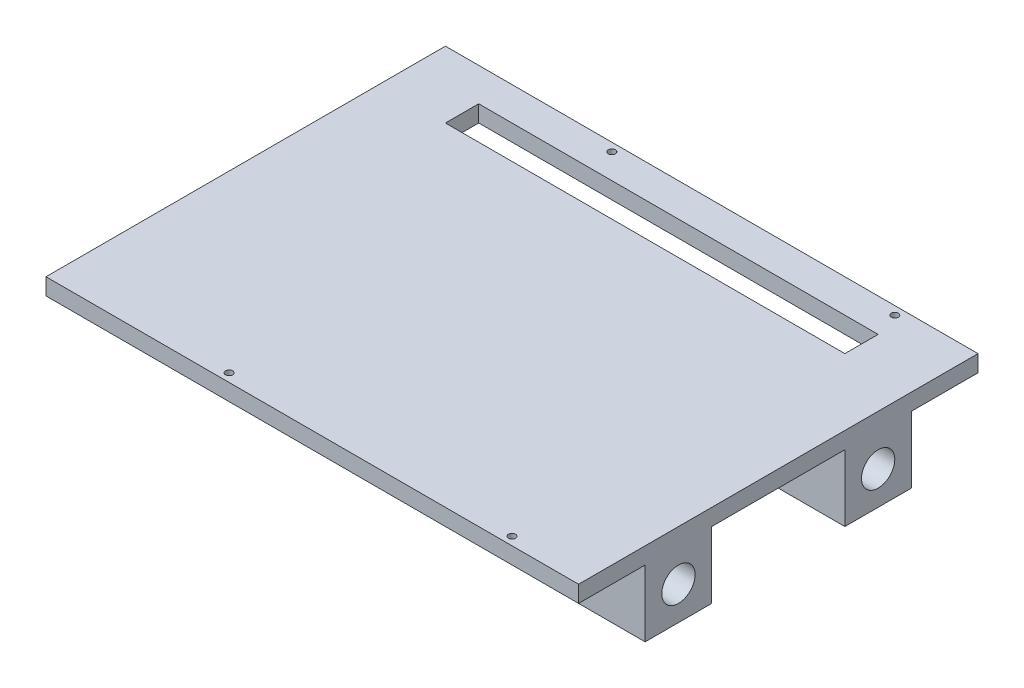
SolidWorks part; units mm, degrees
ref_plane "Front Plane" through (0, 0, 0) normal (0, 0, 1) x (1, 0, 0)
ref_plane "Top Plane" through (0, 0, 0) normal (0, 1, 0) x (1, 0, 0)
ref_plane "Right Plane" through (0, 0, 0) normal (1, 0, 0) x (0, 0, -1)
sketch "Sketch2" plane through (0, 0, 0) normal (0, 1, 0) x (1, 0, 0)
  line L1 (-101.6, -76.2) -> (101.6, -76.2)
  line L2 (-101.6, -76.2) -> (-101.6, 76.2)
  line L3 (-101.6, 76.2) -> (101.6, 76.2)
  line L4 (101.6, -76.2) -> (101.6, 76.2)
  line L5 (-101.6, -76.2) -> (101.6, 76.2) construction
  line L6 (-101.6, 76.2) -> (101.6, -76.2) construction
  point P0 (0, 0)
  dimension "D1" = 203.2
  dimension "D2" = 152.4
extrude "Boss-Extrude1" add sketch "Sketch2" along normal blind 6.35
sketch "Sketch3" plane through (0, 6.35, 0) normal (0, 1, 0) x (1, 0, 0)
  line L0 (-101.6, 0) -> (101.6, 0) construction
  line L1 (-101.6, 76.2) -> (-101.6, -76.2) construction
  line L2 (101.6, -76.2) -> (101.6, 76.2) construction
  line L3 (0, 76.2) -> (0, -76.2) construction
  line L4 (101.6, 76.2) -> (-101.6, 76.2) construction
  line L5 (-101.6, -76.2) -> (101.6, -76.2) construction
  line L7 (-76.2, 63.5) -> (76.2, 63.5)
  line L8 (-76.2, 63.5) -> (-76.2, 50.8)
  line L9 (-76.2, 50.8) -> (76.2, 50.8)
  line L10 (76.2, 63.5) -> (76.2, 50.8)
  line L11 (-76.2, 63.5) -> (76.2, 50.8) construction
  line L12 (-76.2, 50.8) -> (76.2, 63.5) construction
  point P12 (0, 57.15)
  dimension "D1" = 12.7
  dimension "D2" = 152.4
  dimension "D3" = 12.7
extrude "Cut-Extrude1" cut sketch "Sketch3" against normal blind 6.35
sketch "Sketch4" plane through (0, 0, 0) normal (0, -1, 0) x (1, 0, 0)
  line L0 (-101.6, -76.2) -> (-101.6, 76.2) construction
  line L1 (-101.6, 50.8) -> (-50.8, 50.8)
  line L2 (-101.6, 50.8) -> (-101.6, 25.4)
  line L3 (-101.6, 25.4) -> (-50.8, 25.4)
  line L4 (-50.8, 50.8) -> (-50.8, 25.4)
  line L5 (0, 76.2) -> (0, -76.2) construction
  line L6 (-101.6, 76.2) -> (101.6, 76.2) construction
  line L7 (101.6, -76.2) -> (-101.6, -76.2) construction
  line L8 (-101.6, 0) -> (101.6, 0) construction
  line L9 (101.6, 76.2) -> (101.6, -76.2) construction
  line L10 (101.6, 25.4) -> (50.8, 25.4)
  line L11 (50.8, 50.8) -> (50.8, 25.4)
  line L12 (101.6, 50.8) -> (50.8, 50.8)
  line L13 (101.6, 50.8) -> (101.6, 25.4)
  line L14 (101.6, -50.8) -> (101.6, -25.4)
  line L15 (101.6, -50.8) -> (50.8, -50.8)
  line L16 (50.8, -50.8) -> (50.8, -25.4)
  line L17 (101.6, -25.4) -> (50.8, -25.4)
  line L18 (-101.6, -25.4) -> (-50.8, -25.4)
  line L19 (-50.8, -50.8) -> (-50.8, -25.4)
  line L20 (-101.6, -50.8) -> (-50.8, -50.8)
  line L21 (-101.6, -50.8) -> (-101.6, -25.4)
  dimension "D1" = 25.4
  dimension "D2" = 50.8
  dimension "D3" = 25.4
sketch "Sketch6" plane through (0, 0, 0) normal (0, -1, 0) x (1, 0, 0)
  line L0 (0, -50.8) -> (0, -63.5) construction
  line L1 (-76.2, -50.8) -> (76.2, -50.8) construction
  line L2 (76.2, -63.5) -> (-76.2, -63.5) construction
extrude "Boss-Extrude2" add sketch "Sketch4" along normal blind 25.4
sketch "Sketch7" plane through (-101.6, 0, 0) normal (-1, 0, 0) x (0, 0, 1)
  line L0 (-38.1, -25.4) -> (-38.1, 6.35) construction
  line L1 (-25.4, -25.4) -> (-50.8, -25.4) construction
  line L2 (-76.2, 6.35) -> (76.2, 6.35) construction
  line L3 (-50.8, -12.7) -> (-25.4, -12.7) construction
  line L4 (-50.8, -25.4) -> (-50.8, 0) construction
  line L5 (-25.4, -25.4) -> (-25.4, 0) construction
  line L6 (38.1, -25.4) -> (38.1, 6.35) construction
  line L7 (50.8, -25.4) -> (25.4, -25.4) construction
  line L8 (25.4, -12.7) -> (50.8, -12.7) construction
  line L9 (25.4, -25.4) -> (25.4, 0) construction
  line L10 (50.8, -25.4) -> (50.8, 0) construction
  circle A0 centre (-38.1, -12.7) radius 6.35
  circle A1 centre (38.1, -12.7) radius 6.35
  dimension "D1" = 12.7
  dimension "D2" = 12.7
extrude "Cut-Extrude2" cut sketch "Sketch7" against normal blind 50.8
sketch "Sketch8" plane through (101.6, 0, 0) normal (1, 0, 0) x (0, 0, -1)
  line L0 (-50.8, -12.7) -> (50.8, -12.7) construction
  line L1 (-50.8, -25.4) -> (-50.8, 0) construction
  line L2 (50.8, -25.4) -> (50.8, 0) construction
  line L3 (-38.1, -25.4) -> (-38.1, 6.35) construction
  line L4 (50.8, -25.4) -> (25.4, -25.4) construction
  line L5 (38.1, -25.4) -> (38.1, 6.35) construction
  line L6 (-76.2, 6.35) -> (76.2, 6.35) construction
  line L7 (-25.4, -25.4) -> (-50.8, -25.4) construction
  circle A0 centre (-38.1, -12.7) radius 6.35
  circle A1 centre (38.1, -12.7) radius 6.35
  dimension "D1" = 12.7
  dimension "D2" = 12.7
extrude "Cut-Extrude3" cut sketch "Sketch8" against normal blind 50.8
ref_plane "Plane1" through (0, 0, 0) normal (-1, 0, 0) x (0, 0, 1)
ref_point "Point1"
sketch "Sketch12" plane through (0, 6.35, 0) normal (0, 1, 0) x (1, 0, 0)
  line L0 (101.6, 76.2) -> (-101.6, 76.2) construction
  line L1 (-38.1204, 76.2) -> (25.3796, 76.2)
  line L2 (-38.1204, 76.2) -> (-38.1204, 63.5)
  line L3 (-38.1204, 63.5) -> (25.3796, 63.5)
  line L4 (25.3796, 76.2) -> (25.3796, 63.5)
  line L5 (76.2, 63.5) -> (-76.2, 63.5) construction
  dimension "D1" = 63.5
hole_wizard "#6-32 Tapped Hole1" positions "Sketch13" profile "Sketch14" tap size "#6-32" standard "ANSI Inch"
sketch "Sketch13" plane through (0, 6.35, 0) normal (0, 1, 0) x (1, 0, 0)
  point P12 (-34.925, -73.025)
  point P15 (-34.925, 73.025)
  point P18 (73.025, 73.025)
  point P21 (73.025, -73.025)
  point P24 (0, 0)
  point P25 (0, 0)
cosmetic thread "Hole Thread6"
cosmetic thread "Hole Thread7"
cosmetic thread "Hole Thread8"
cosmetic thread "Hole Thread9"
sketch "Sketch14" plane through (-34.925, 6.35, 73.025) normal (1, 0, 0) x (0, 0, 1)
  line L0 (0, 0) -> (0, 13.5127)
  line L1 (0, 13.5127) -> (1.3525, 12.7)
  line L2 (1.3525, 12.7) -> (1.3525, 0)
  line L5 (1.3525, 0) -> (0, 0)
  line L10 (0, 13.5127) -> (-1.3526, 12.7) construction
  line L11 (0, -6.35) -> (0, 107.95) construction
  dimension "Tap Drill Dia." = 2.7051
  dimension "Tap Drill Depth" = 12.7
  dimension "Drill Angle" = 118
